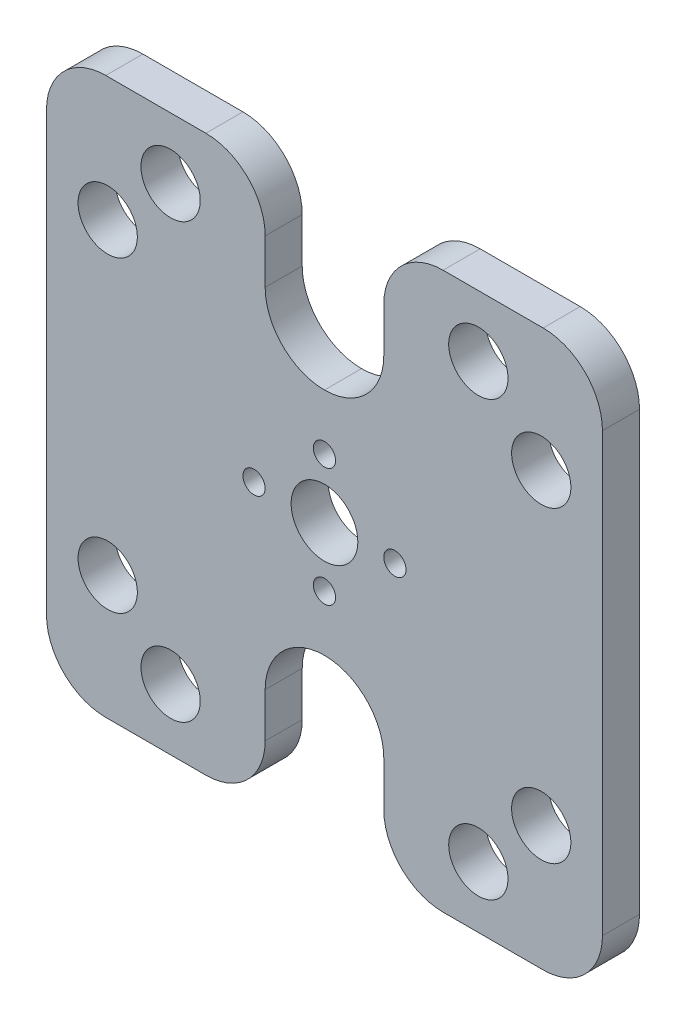
SolidWorks part; units mm, degrees
ref_plane "Front Plane" through (0, 0, 0) normal (0, 0, 1) x (1, 0, 0)
ref_plane "Top Plane" through (0, 0, 0) normal (0, 1, 0) x (1, 0, 0)
ref_plane "Right Plane" through (0, 0, 0) normal (1, 0, 0) x (0, 0, -1)
sketch "Sketch1" plane through (0, 0, 0) normal (0, 0, 1) x (-1, 0, 0)
  line L0 (0, 8) -> (0, -8) construction
  line L1 (9.5, 0) -> (-9.5, 0) construction
  line L2 (29.2426, 20.7574) -> (20.7574, 29.2426) construction
  line L3 (37.5, -37.5) -> (-37.5, -37.5)
  line L4 (37.5, -37.5) -> (37.5, 37.5)
  line L5 (37.5, 37.5) -> (-37.5, 37.5)
  line L6 (-37.5, -37.5) -> (-37.5, 37.5)
  line L7 (37.5, -37.5) -> (-37.5, 37.5) construction
  line L8 (37.5, 37.5) -> (-37.5, -37.5) construction
  line L9 (-25, -25) -> (25, -25) construction
  line L10 (-25, -25) -> (-25, 25) construction
  line L11 (-25, 25) -> (25, 25) construction
  line L12 (25, -25) -> (25, 25) construction
  line L13 (-25, -25) -> (25, 25) construction
  line L14 (-25, 25) -> (25, -25) construction
  circle A0 centre (9.5, 0) radius 1.5
  circle A1 centre (-9.5, 0) radius 1.5
  circle A2 centre (0, -8) radius 1.5
  circle A3 centre (0, 8) radius 1.5
  circle A10 centre (0, 0) radius 4.5
  circle A11 centre (20.7574, 29.2426) radius 4
  circle A12 centre (29.2426, 20.7574) radius 4
  circle A13 centre (-29.2426, -20.7574) radius 4
  circle A14 centre (-20.7574, -29.2426) radius 4
  circle A15 centre (20.7574, -29.2426) radius 4
  circle A16 centre (29.2426, -20.7574) radius 4
  circle A17 centre (-20.7574, 29.2426) radius 4
  circle A18 centre (-29.2426, 20.7574) radius 4
  point P3 (0, 0)
  point P14 (0, 0)
  point P22 (25, 25)
  dimension "D1" = 75
  dimension "D4" = 3
  dimension "D2" = 50
extrude "Boss-Extrude1" add sketch "Sketch1" along normal blind 5
sketch "Sketch3" plane through (0, 0, 5) normal (0, 0, 1) x (1, 0, 0)
  line L0 (0, 0) -> (0, 26.5) construction
  line L1 (37.5, 37.5) -> (-37.5, 37.5) construction
  line L2 (-8, 15.5) -> (8, 15.5)
  line L3 (-8, 15.5) -> (-8, 37.5)
  line L4 (-8, 37.5) -> (8, 37.5)
  line L5 (8, 15.5) -> (8, 37.5)
  line L6 (-8, 15.5) -> (8, 37.5) construction
  line L7 (-8, 37.5) -> (8, 15.5) construction
  line L8 (0, 0) -> (-37.5, 0) construction
  line L9 (-37.5, 37.5) -> (-37.5, -37.5) construction
  line L10 (-8, -37.5) -> (8, -37.5)
  line L11 (8, -15.5) -> (8, -37.5)
  line L12 (-8, -15.5) -> (8, -15.5)
  line L13 (-8, -15.5) -> (-8, -37.5)
extrude "Cut-Extrude1" cut sketch "Sketch3" against normal up to surface (5 mm away) up to face at (0, 0, 0)
fillet "Fillet1" radius 8 12 edges at (-37.5, -37.5, 2.5) (-8, -37.5, 2.5) (8, -15.5, 2.5) (-8, -15.5, 2.5) (8, -37.5, 2.5) (37.5, -37.5, 2.5) (37.5, 37.5, 2.5) (8, 37.5, 2.5) (8, 15.5, 2.5) (-8, 15.5, 2.5) (-8, 37.5, 2.5) (-37.5, 37.5, 2.5)
